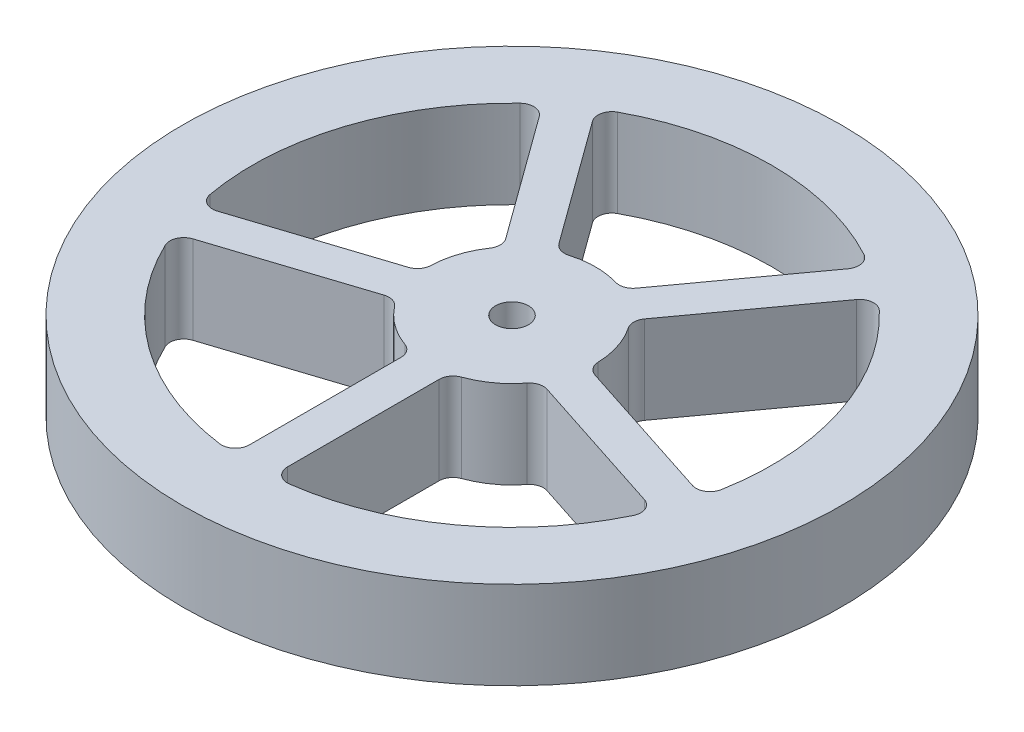
SolidWorks part; units mm, degrees
material "Nylon 6/10"
ref_plane "Front Plane" through (0, 0, 0) normal (0, 0, 1) x (1, 0, 0)
ref_plane "Top Plane" through (0, 0, 0) normal (0, 1, 0) x (1, 0, 0)
ref_plane "Right Plane" through (0, 0, 0) normal (1, 0, 0) x (0, 0, -1)
sketch "Sketch1" plane through (0, 0, 0) normal (0, 1, 0) x (1, 0, 0)
  circle A0 centre (0, 0) radius 30
  circle A1 centre (0, 0) radius 1.5
  dimension "D1" = 60
  dimension "D2" = 3
extrude "Boss-Extrude1" add sketch "Sketch1" along normal blind 8
sketch "Sketch2" plane through (0, 8, 0) normal (0, 1, 0) x (1, 0, 0)
  circle A0 centre (0, 0) radius 7.62
  circle A1 centre (0, 0) radius 23.65
  circle A3 centre (0, 0) radius 30 construction
  dimension "D1" = 15.24
  dimension "D2" = 6.35
extrude "Cut-Extrude1" cut sketch "Sketch2" against normal up to surface (8 mm away) up to face at (0, 0, 30)
sketch "Sketch3" plane through (0, 8, 0) normal (0, 1, 0) x (1, 0, 0)
  line L0 (-1.7345, -8.3669) -> (-1.7345, -22.1774)
  line L1 (1.7345, -8.3669) -> (1.7345, -22.1774)
  line L3 (0, -7.62) -> (0, -23.65) construction
  line L4 (-1.7345, -15.2722) -> (0, -15.635) construction
  line L5 (0, -15.635) -> (1.7345, -15.2722) construction
  circle A0 centre (0, 0) radius 7.62 construction
  circle A1 centre (0, 0) radius 23.65 construction
  arc A2 (-3.175, -23.4359) -> (3.175, -23.4359) centre (0, 0) ccw
  arc A3 (-2.5753, -7.1716) -> (2.5753, -7.1716) centre (0, 0) ccw
  arc A4 (-3.175, -23.4359) -> (-1.7345, -22.1774) centre (-3.0045, -22.1774) ccw
  arc A5 (1.7345, -22.1774) -> (3.175, -23.4359) centre (3.0045, -22.1774) ccw
  arc A6 (-2.5753, -7.1716) -> (-1.7345, -8.3669) centre (-3.0045, -8.3669) cw
  arc A7 (1.7345, -8.3669) -> (2.5753, -7.1716) centre (3.0045, -8.3669) cw
  dimension "D3" = 1.27
  dimension "D4" = 1.27
  dimension "D5" = 1.27
  dimension "D2" = 6.35
extrude "Boss-Extrude2" add sketch "Sketch3" against normal up to surface (8 mm away) contours L0 A4 A2 A5 L1 A7 A3 A6 up to face at (0, 0, 23.65)
ref_axis "Axis1" through (0, 8, 0) along (0, -1, 0)
pattern_circular "CirPattern1" count 5 over 360 about axis through (0, 8, 0) along (0, -1, 0) of "Boss-Extrude2"
